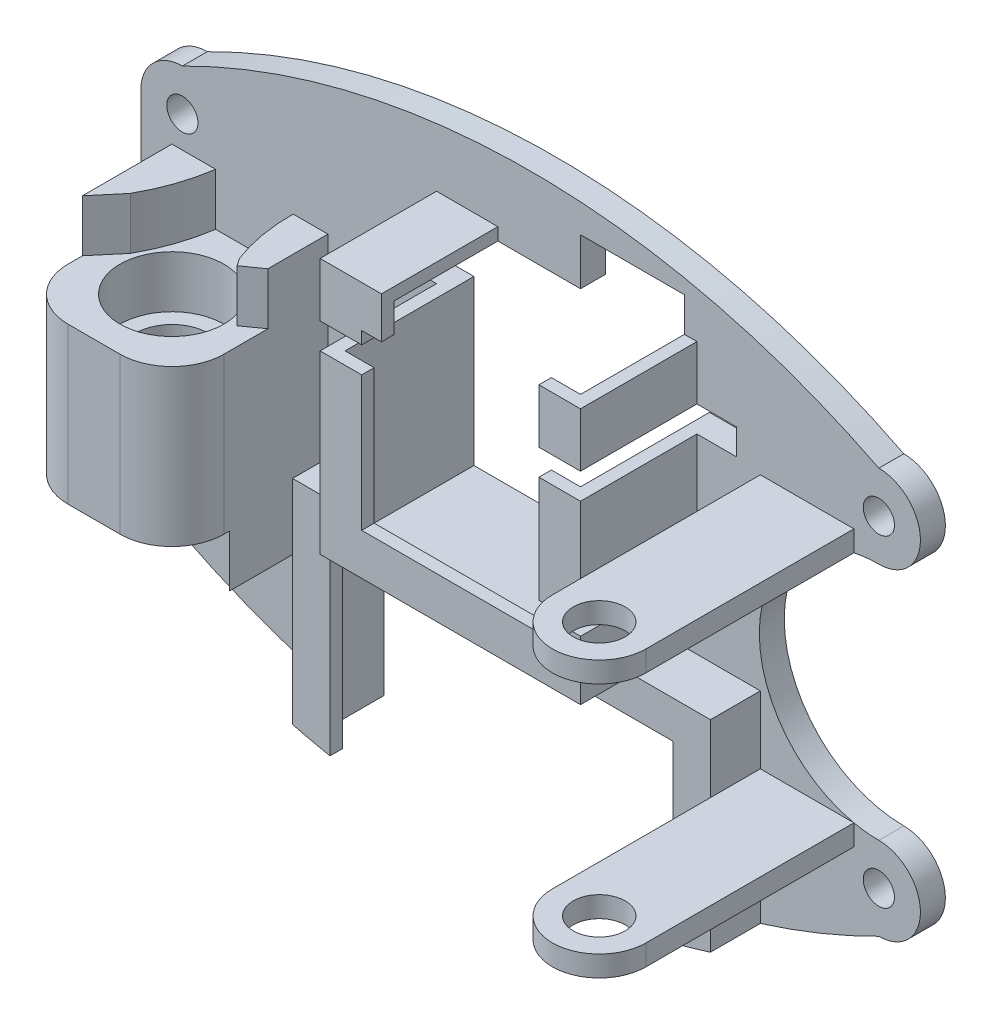
SolidWorks part; units mm, degrees
material "ABS"
ref_plane "Alzado" through (0, 0, 0) normal (0, 0, 1) x (1, 0, 0)
ref_plane "Planta" through (0, 0, 0) normal (0, 1, 0) x (1, 0, 0)
ref_plane "Vista lateral" through (0, 0, 0) normal (1, 0, 0) x (0, 0, -1)
sketch "Croquis1" plane through (0, 0, 0) normal (0, 0, 1) x (1, 0, 0)
  line L0 (-65.9407, 48.6885) -> (-65.9407, 17.6885)
  line L1 (-61.9407, 52.6885) -> (5.0593, 52.6885) construction
  line L2 (-61.9407, 13.6885) -> (5.0593, 13.6885) construction
  line L3 (-28.4407, 52.6885) -> (-28.4407, 60.6885) construction
  line L4 (-28.4407, 13.6885) -> (-28.4407, 5.6885) construction
  circle A0 centre (-61.9407, 48.6885) radius 1.5
  circle A1 centre (5.0593, 48.6885) radius 1.5
  circle A2 centre (5.0593, 17.6885) radius 1.5
  circle A3 centre (-61.9407, 17.6885) radius 1.5
  arc A4 (-61.9407, 52.6885) -> (-65.9407, 48.6885) centre (-61.9407, 48.6885) ccw
  arc A5 (-65.9407, 17.6885) -> (-61.9407, 13.6885) centre (-61.9407, 17.6885) ccw
  arc A6 (-61.9407, 13.6885) -> (5.0593, 13.6885) centre (-28.4407, 79.8291) ccw
  arc A7 (5.0593, 13.6885) -> (5.0593, 21.6885) centre (5.0593, 17.6885) ccw
  arc A8 (5.0593, 44.6885) -> (5.0593, 21.6885) centre (5.0593, 33.1885) ccw
  arc A9 (5.0593, 44.6885) -> (5.0593, 52.6885) centre (5.0593, 48.6885) ccw
  arc A10 (5.0593, 52.6885) -> (-61.9407, 52.6885) centre (-28.4407, -13.4521) ccw
  dimension "D2" = 8
  dimension "D3" = 8
  dimension "D5" = 4
  dimension "D6" = 4
  dimension "D7" = 3
  dimension "D8" = 3
  dimension "D9" = 4
  dimension "D10" = 3
  dimension "D11" = 4
  dimension "D12" = 3
  dimension "D13" = 11.5
  dimension "D1" = 67
  dimension "D4" = 31
extrude "Saliente-Extruir1" add sketch "Croquis1" along normal blind 2.4
sketch "Croquis3" plane through (0, 0, 2.4) normal (0, 0, 1) x (1, 0, 0)
  line L0 (-12.4407, 54.4855) -> (-12.4407, 29.8355)
  line L1 (-36.2907, 53.2855) -> (-13.6407, 53.2855)
  line L2 (-36.2907, 53.2855) -> (-36.2907, 31.0355)
  line L3 (-36.2907, 31.0355) -> (-13.6407, 31.0355)
  line L4 (-13.6407, 53.2855) -> (-13.6407, 31.0355)
  line L5 (-37.4907, 29.8355) -> (-12.4407, 29.8355)
  line L6 (-37.4907, 54.4855) -> (-37.4907, 29.8355)
  line L7 (-37.4907, 54.4855) -> (-12.4407, 54.4855)
  line L8 (-39.8407, 27.8355) -> (-39.8407, 7.4355) construction
  line L9 (-38.6407, 26.6355) -> (-13.6407, 26.6355) construction
  line L10 (-38.6407, 26.6355) -> (-38.6407, 8.6355) construction
  line L11 (-38.6407, 8.6355) -> (-13.6407, 8.6355) construction
  line L12 (-13.6407, 26.6355) -> (-13.6407, 8.6355) construction
  line L13 (-39.8407, 7.4355) -> (-12.4407, 7.4355) construction
  line L14 (-12.4407, 27.8355) -> (-12.4407, 7.4355) construction
  line L15 (-39.8407, 27.8355) -> (-12.4407, 27.8355) construction
  line L16 (-6.4407, 33.1885) -> (-12.4407, 33.1885) construction
  arc A0 (5.0593, 44.6885) -> (5.0593, 21.6885) centre (5.0593, 33.1885) ccw construction
  arc A1 (-61.9407, 13.6885) -> (5.0593, 13.6885) centre (-28.4407, 79.8291) ccw construction
  dimension "D1" = 22.65
  dimension "D2" = 22.25
  dimension "D4" = 18
  dimension "D5" = 25
  dimension "D7" = 6
  dimension "D8" = 2
  dimension "D3" = 1.2
  dimension "D6" = 1.2
extrude "Saliente-Extruir2" add sketch "Croquis3" along normal blind 10
sketch "Croquis4" plane through (0, 0, 12.4) normal (0, 0, 1) x (1, 0, 0)
  line L0 (-33.4907, 50.4855) -> (-33.4907, 33.8355)
  line L1 (-37.4907, 54.4855) -> (-12.4407, 54.4855)
  line L2 (-37.4907, 54.4855) -> (-37.4907, 29.8355)
  line L3 (-37.4907, 29.8355) -> (-12.4407, 29.8355)
  line L4 (-12.4407, 54.4855) -> (-12.4407, 29.8355)
  line L5 (-33.4907, 33.8355) -> (-16.4407, 33.8355)
  line L6 (-16.4407, 50.4855) -> (-16.4407, 33.8355)
  line L7 (-33.4907, 50.4855) -> (-16.4407, 50.4855)
  dimension "D1" = 4
extrude "Saliente-Extruir3" add sketch "Croquis4" along normal blind 1.2
sketch "Croquis5" plane through (0, 0, 13.6) normal (0, 0, 1) x (1, 0, 0)
  line L0 (-33.4907, 50.4855) -> (-33.4907, 33.8355) construction
  line L1 (-33.4907, 49.2855) -> (-37.4907, 49.2855)
  line L2 (-33.4907, 49.2855) -> (-33.4907, 46.7855)
  line L3 (-33.4907, 46.7855) -> (-37.4907, 46.7855)
  line L4 (-37.4907, 49.2855) -> (-37.4907, 46.7855)
  line L5 (-37.4907, 54.4855) -> (-37.4907, 29.8355) construction
  line L6 (-12.4407, 54.4855) -> (-37.4907, 54.4855) construction
  line L7 (-16.4407, 50.4855) -> (-31.5907, 50.4855)
  line L8 (-16.4407, 50.4855) -> (-16.4407, 54.4855)
  line L9 (-16.4407, 54.4855) -> (-31.5907, 54.4855)
  line L10 (-31.5907, 50.4855) -> (-31.5907, 54.4855)
  line L11 (-16.4407, 50.4855) -> (-33.4907, 50.4855) construction
  line L12 (-16.4407, 33.8355) -> (-16.4407, 50.4855) construction
  line L17 (-12.4407, 29.8355) -> (-12.4407, 54.4855) construction
  line L19 (-16.4407, 35.5355) -> (-12.4407, 35.5355)
  line L20 (-16.4407, 35.5355) -> (-16.4407, 36.5355)
  line L21 (-16.4407, 36.5355) -> (-12.4407, 36.5355)
  line L22 (-12.4407, 35.5355) -> (-12.4407, 36.5355)
  line L23 (-37.4907, 29.8355) -> (-12.4407, 29.8355) construction
  line L24 (-24.9657, 33.8355) -> (-24.9657, 50.4855) construction
  line L25 (-33.4907, 33.8355) -> (-16.4407, 33.8355) construction
  line L26 (-12.4407, 49.2855) -> (-12.4407, 46.7855)
  line L27 (-16.4407, 46.7855) -> (-12.4407, 46.7855)
  line L28 (-16.4407, 49.2855) -> (-16.4407, 46.7855)
  line L29 (-16.4407, 49.2855) -> (-12.4407, 49.2855)
  dimension "D1" = 5.2
  dimension "D2" = 2.5
  dimension "D3" = 15.15
  dimension "D4" = 5.7
  dimension "D5" = 1
extrude "Cortar-Extruir1" cut sketch "Croquis5" against normal up to vertex (11.2 mm away) up to point (-37.4907, 29.8355, 2.4)
sketch "Croquis8" plane through (0, 0, 2.4) normal (0, 0, 1) x (1, 0, 0)
  line L0 (-6.4407, 33.1885) -> (-65.9407, 33.1885) construction
  line L1 (-65.9407, 48.6885) -> (-65.9407, 17.6885) construction
  line L3 (-62.9407, 40.6885) -> (-47.9407, 40.6885)
  line L4 (-62.9407, 40.6885) -> (-62.9407, 25.6885)
  line L5 (-62.9407, 25.6885) -> (-47.9407, 25.6885)
  line L6 (-47.9407, 40.6885) -> (-47.9407, 25.6885)
  arc A0 (5.0593, 44.6885) -> (5.0593, 21.6885) centre (5.0593, 33.1885) ccw construction
  point P11 (-47.9407, 33.1885)
  dimension "D1" = 15
  dimension "D2" = 15
  dimension "D3" = 3
extrude "Saliente-Extruir5" add sketch "Croquis8" along normal blind 15
sketch "Croquis10" plane through (0, 25.6885, 0) normal (0, -1, 0) x (1, 0, 0)
  line L0 (-62.9407, 2.4) -> (-47.9407, 2.4) construction
  line L1 (-62.9407, 17.4) -> (-47.9407, 17.4) construction
  circle A0 centre (-55.4407, 9.9) radius 5
  point P7 (-55.4407, 17.4)
  dimension "D1" = 10
  dimension "D2" = 7.5
extrude "Cortar-Extruir2" cut sketch "Croquis10" against normal blind 5
extrude "Cortar-Extruir3" cut sketch "Croquis10<2>" along normal blind 5 from surface starting at face at (-55.4407, 40.6885, 9.9)
sketch "Croquis10<2>" plane through (0, 25.6885, 0) normal (0, -1, 0) x (1, 0, 0) same geometry as "Croquis10"
sketch "Croquis11" plane through (0, 30.6885, 0) normal (0, -1, 0) x (1, 0, 0)
  circle A0 centre (-55.4407, 9.9) radius 3.5
  dimension "D1" = 7
extrude "Cortar-Extruir4" cut sketch "Croquis11" against normal up to surface (5 mm away) up to face at (-50.4407, 35.6885, 9.9)
sketch "Croquis12" plane through (0, 0, 2.4) normal (0, 0, 1) x (1, 0, 0)
  line L0 (-24.9657, 53.2855) -> (-24.9657, 31.0355) construction
  line L1 (-36.2907, 53.2855) -> (-13.6407, 53.2855)
  line L2 (-36.2907, 53.2855) -> (-36.2907, 49.2855)
  line L3 (-36.2907, 31.0355) -> (-13.6407, 31.0355)
  line L5 (-36.2907, 49.2855) -> (-41.2907, 49.2855)
  line L7 (-36.2907, 46.7855) -> (-41.2907, 46.7855)
  line L8 (-41.2907, 49.2855) -> (-41.2907, 46.7855)
  line L9 (-36.2907, 46.7855) -> (-36.2907, 31.0355)
  line L10 (-13.6407, 46.7855) -> (-13.6407, 31.0355)
  line L11 (-8.6407, 49.2855) -> (-8.6407, 46.7855)
  line L12 (-13.6407, 46.7855) -> (-8.6407, 46.7855)
  line L13 (-13.6407, 49.2855) -> (-8.6407, 49.2855)
  line L14 (-13.6407, 53.2855) -> (-13.6407, 49.2855)
  line L15 (-37.4907, 46.7855) -> (-36.2907, 46.7855) construction
  dimension "D1" = 5
extrude "Cortar-Extruir5" cut sketch "Croquis12" against normal up to vertex (2.4 mm away) up to point (5.0593, 52.6885, 0)
sketch "Croquis13" plane through (0, 0, 2.4) normal (0, 0, 1) x (1, 0, 0)
  line L0 (-12.4407, 49.2855) -> (-12.4407, 54.4855) construction
  line L1 (-23.6407, 57.7855) -> (-13.6407, 57.7855)
  line L2 (-23.6407, 57.7855) -> (-23.6407, 53.2855)
  line L3 (-23.6407, 53.2855) -> (-13.6407, 53.2855)
  line L4 (-13.6407, 57.7855) -> (-13.6407, 53.2855)
  line L5 (-16.4407, 53.2855) -> (-31.5907, 53.2855) construction
  dimension "D1" = 1.2
  dimension "D2" = 4.5
  dimension "D3" = 10
extrude "Cortar-Extruir6" cut sketch "Croquis13" along normal blind 10 and the other way up to vertex (2.4 mm away) other way up to point (5.0593, 52.6885, 0)
fillet "Redondeo1" radius 5 2 edges at (-47.9407, 33.1885, 17.4) (-62.9407, 33.1885, 17.4)
sketch "Croquis14" plane through (0, 0, 2.4) normal (0, 0, 1) x (1, 0, 0)
  line L0 (-37.4907, 29.8355) -> (-12.4407, 29.8355) construction
  line L1 (-44.9407, 26.8355) -> (-7.9407, 26.8355)
  line L2 (-44.9407, 26.8355) -> (-44.9407, 1.8355)
  line L3 (-44.9407, 1.8355) -> (-7.9407, 1.8355)
  line L4 (-7.9407, 26.8355) -> (-7.9407, 1.8355)
  line L5 (-47.9407, 25.6885) -> (-47.9407, 40.6885) construction
  line L6 (-24.9657, 29.8355) -> (-24.9657, 26.8355) construction
  line L7 (-33.9907, 29.8355) -> (-30.9907, 29.8355)
  line L8 (-33.9907, 29.8355) -> (-33.9907, 27.8355)
  line L9 (-33.9907, 27.8355) -> (-30.9907, 27.8355)
  line L10 (-30.9907, 29.8355) -> (-30.9907, 27.8355)
  dimension "D1" = 37
  dimension "D2" = 25
  dimension "D3" = 3
  dimension "D4" = 3
  dimension "D5" = 2
  dimension "D6" = 3
  dimension "D7" = 3.5
extrude "Cortar-Extruir7" cut sketch "Croquis14" against normal up to next
sketch "Croquis15" plane through (0, 0, 2.4) normal (0, 0, 1) x (1, 0, 0)
  line L0 (-44.9407, 7.5479) -> (-44.9407, 26.8355)
  line L1 (-44.9407, 26.8355) -> (-33.9907, 26.8355)
  line L2 (-7.9407, 26.8355) -> (-7.9407, 8.579)
  line L3 (-46.5407, 7.9318) -> (-46.5407, 28.4355)
  line L4 (-46.5407, 28.4355) -> (-33.9907, 28.4355)
  line L5 (-33.9907, 29.8355) -> (-33.9907, 27.8355) construction
  line L6 (-33.9907, 28.4355) -> (-33.9907, 26.8355)
  line L7 (-30.9907, 28.4355) -> (-30.9907, 26.8355)
  line L8 (-30.9907, 27.8355) -> (-30.9907, 29.8355) construction
  line L9 (-30.9907, 26.8355) -> (-7.9407, 26.8355)
  line L10 (-30.9907, 28.4355) -> (-6.3407, 28.4355)
  line L11 (-6.3407, 28.4355) -> (-6.3407, 9.0589)
  arc A0 (-61.9407, 13.6885) -> (-44.9407, 7.5479) centre (-28.4407, 79.8291) ccw construction
  arc A1 (-7.9407, 8.579) -> (5.0593, 13.6885) centre (-28.4407, 79.8291) ccw construction
  arc A9 (-61.9407, 13.6885) -> (-44.9407, 7.5479) centre (-28.4407, 79.8291) ccw
  arc A10 (-46.5407, 7.9318) -> (-44.9407, 7.5479) centre (-28.4407, 79.8291) ccw
  arc A12 (-7.9407, 8.579) -> (5.0593, 13.6885) centre (-28.4407, 79.8291) ccw
  arc A13 (-7.9407, 8.579) -> (-6.3407, 9.0589) centre (-28.4407, 79.8291) ccw
  dimension "D1" = 1.6
  dimension "D2" = 1.6
  dimension "D3" = 1.6
  dimension "D4" = 1.6
  dimension "D5" = 0
  dimension "D6" = 0
extrude "Saliente-Extruir6" add sketch "Croquis15" along normal blind 3.6
sketch "Croquis16" plane through (0, 0, 6) normal (0, 0, 1) x (1, 0, 0)
  line L0 (-33.9907, 28.4355) -> (-46.5407, 28.4355)
  line L3 (-46.5407, 28.4355) -> (-46.5407, 7.9318)
  line L4 (-30.9907, 28.4355) -> (-6.3407, 28.4355)
  line L5 (-6.3407, 28.4355) -> (-6.3407, 9.0589)
  line L11 (-42.9407, 24.8355) -> (-33.9907, 24.8355)
  line L12 (-42.9407, 7.5479) -> (-42.9407, 24.8355)
  line L13 (-42.9407, 24.8355) -> (-33.9907, 24.8355)
  line L14 (-42.9407, 7.1202) -> (-42.9407, 24.8355)
  line L16 (-33.9907, 28.4355) -> (-33.9907, 24.8355)
  line L17 (-30.9907, 28.4355) -> (-30.9907, 24.8355)
  line L18 (-9.9407, 24.8355) -> (-9.9407, 8.579)
  line L19 (-30.9907, 24.8355) -> (-9.9407, 24.8355)
  line L20 (-9.9407, 24.8355) -> (-9.9407, 8.0337)
  line L21 (-30.9907, 24.8355) -> (-9.9407, 24.8355)
  arc A0 (-46.5407, 7.9318) -> (-42.9407, 7.1202) centre (-28.4407, 79.8291) ccw
  arc A1 (-9.9407, 8.0337) -> (-6.3407, 9.0589) centre (-28.4407, 79.8291) ccw
  dimension "D1" = 2
  dimension "D2" = 2
extrude "Saliente-Extruir7" add sketch "Croquis16" along normal blind 1.2
sketch "Croquis20" plane through (0, 25.6885, 0) normal (0, -1, 0) x (1, 0, 0)
  line L0 (-62.9407, 2.4) -> (-62.9407, 11.012)
  line L1 (-62.9407, 12.4) -> (-62.9407, 2.4) construction
  line L2 (-62.9407, 11.012) -> (-60.8397, 8.5116)
  line L4 (-62.9407, 2.4) -> (-47.9407, 2.4) construction
  line L5 (-58.7388, 2.4) -> (-62.9407, 2.4)
  line L6 (-47.9407, 2.4) -> (-47.9407, 11.8496)
  line L7 (-47.9407, 12.4) -> (-47.9407, 2.4) construction
  line L10 (-51.275, 2.4) -> (-47.9407, 2.4)
  line L12 (-50.162, 8.702) -> (-47.9407, 11.8496)
  arc A1 (-58.7388, 2.4) -> (-60.8397, 8.5116) centre (-76.1554, -0.1704) ccw
  arc A3 (-50.162, 8.702) -> (-51.275, 2.4) centre (-34.3459, 2.6594) ccw
extrude "Saliente-Extruir8" add sketch "Croquis20" along normal blind 5
ref_plane "Plano1" through (0, 33.1885, 0) normal (0, -1, 0) x (-1, 0, 0)
mirror "Simetría1" about plane through (0, 33.1885, 0) normal (0, -1, 0) of "Saliente-Extruir8"
sketch "Croquis22" plane through (0, 45.6885, 0) normal (0, 1, 0) x (1, 0, 0)
  line L0 (-47.9407, -11.8496) -> (-49.6705, -9.3985)
  line L2 (-49.6705, -9.3985) -> (-47.9407, -8.1778)
  line L3 (-47.9407, -2.4) -> (-47.9407, -11.8496) construction
  line L4 (-47.9407, -8.1778) -> (-47.9407, -11.8496)
  line L5 (-47.9407, -11.8496) -> (-50.162, -8.702) construction
  point P3 (-50.162, -8.702)
  point P4 (-50.162, -8.702)
  point P5 (-49.0513, -10.2758)
  point P9 (-49.8443, -9.1522)
  dimension "D1" = 3
extrude "Cortar-Extruir8" cut sketch "Croquis22" against normal up to vertex (5 mm away) up to point (-47.9407, 40.6885, 12.4)
sketch "Croquis24" plane through (0, 0, 2.4) normal (0, 0, 1) x (1, 0, 0)
  line L0 (-6.3407, 28.4355) -> (-6.3407, 21.9417)
  line L1 (-6.3407, 9.0589) -> (-6.3407, 28.4355) construction
  line L2 (-6.3407, 21.9417) -> (2.6593, 21.9417)
  arc A0 (5.0593, 44.6885) -> (5.0593, 21.6885) centre (5.0593, 33.1885) ccw construction
  dimension "D1" = 9
ref_plane "Plano2" through (0, 21.9417, 0) normal (0, 1, 0) x (1, 0, 0)
sketch "Croquis25" plane through (0, 21.9417, 0) normal (0, 1, 0) x (1, 0, 0)
  line L0 (-1.8407, -2.4) -> (-1.8407, -22.4) construction
  line L1 (-6.3407, -2.4) -> (2.6593, -2.4) construction
  line L2 (-6.3407, -22.4) -> (-6.3407, -2.4)
  line L5 (2.6593, -22.4) -> (2.6593, -2.4)
  line L6 (-6.3407, -2.4) -> (5.0593, -2.4) construction
  line L7 (-6.3407, -2.4) -> (2.6593, -2.4)
  circle A0 centre (-1.8407, -22.4) radius 2.5
  arc A1 (-6.3407, -22.4) -> (2.6593, -22.4) centre (-1.8407, -22.4) ccw
  dimension "D1" = 5
  dimension "D2" = 9
extrude "Saliente-Extruir9" add sketch "Croquis25" against normal blind 2
mirror "Simetría2" about plane through (0, 33.1885, 0) normal (0, -1, 0) of "Saliente-Extruir9"
